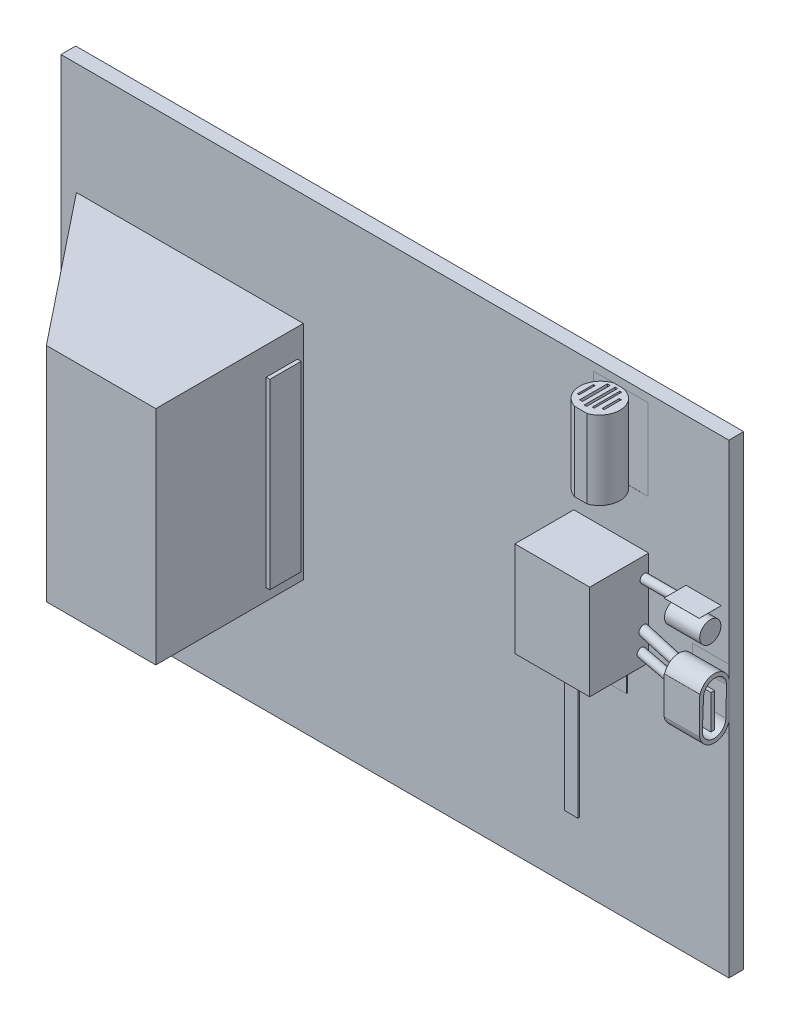
SolidWorks part; units mm, degrees
ref_plane "Front Plane" through (0, 0, 0) normal (0, 0, 1) x (1, 0, 0)
ref_plane "Top Plane" through (0, 0, 0) normal (0, 1, 0) x (1, 0, 0)
ref_plane "Right Plane" through (0, 0, 0) normal (1, 0, 0) x (0, 0, -1)
sketch "Sketch1" plane through (0, 0, 0) normal (0, 0, 1) x (1, 0, 0)
  line L1 (-83.6964, -45.2831) -> (2.5697, -45.2831)
  line L2 (-83.6964, -45.2831) -> (-83.6964, 12.5794)
  line L3 (-83.6964, 12.5794) -> (2.5697, 12.5794)
  line L4 (2.5697, -45.2831) -> (2.5697, 12.5794)
  line L5 (-83.6964, -45.2831) -> (2.5697, 12.5794) construction
  line L6 (-83.6964, 12.5794) -> (2.5697, -45.2831) construction
  point P0 (-40.5634, -16.3519)
extrude "Boss-Extrude1" add sketch "Sketch1" along normal blind 5
sketch "Sketch2" plane through (0, 0, 0) normal (0, 0, -1) x (-1, 0, 0)
  line L1 (50.5486, -38.5474) -> (14.2877, -38.5474)
  line L2 (50.5486, -38.5474) -> (50.5486, 6.6921)
  line L3 (50.5486, 6.6921) -> (14.2877, 6.6921)
  line L4 (14.2877, -38.5474) -> (14.2877, 6.6921)
  line L5 (50.5486, -38.5474) -> (14.2877, 6.6921) construction
  line L6 (50.5486, 6.6921) -> (14.2877, -38.5474) construction
  line L7 (49.8095, -37.7028) -> (15.0267, -37.7028)
  line L8 (49.8095, -37.7028) -> (49.8095, 5.8475)
  line L9 (49.8095, 5.8475) -> (15.0267, 5.8475)
  line L10 (15.0267, -37.7028) -> (15.0267, 5.8475)
  line L11 (49.8095, -37.7028) -> (15.0267, 5.8475) construction
  line L12 (49.8095, 5.8475) -> (15.0267, -37.7028) construction
  point P0 (32.4181, -15.9276)
  point P6 (32.4181, -15.9276)
extrude "Boss-Extrude2" add sketch "Sketch2" along normal blind 1
sketch "Sketch3" plane through (0, 0, 0) normal (0, 0, -1) x (-1, 0, 0)
  circle A0 centre (5.8472, -15.8094) radius 3.5601
extrude "Boss-Extrude3" add sketch "Sketch3" along normal blind 1
sketch "Sketch4" plane through (0, 0, -1) normal (0, 0, -1) x (-1, 0, 0)
  line L0 (7.4982, -13.5037) -> (7.4299, -14.2268)
  line L1 (7.3138, -18.3414) -> (7.3192, -17.6008)
  arc A0 (7.4982, -13.5037) -> (7.3138, -18.3414) centre (5.955, -15.8672) ccw
  arc A1 (7.4299, -14.2268) -> (7.3192, -17.6008) centre (5.955, -15.8672) ccw
extrude "Cut-Extrude2" cut sketch "Sketch4" against normal blind 0.5
sketch "Sketch5" plane through (0, 0, -1) normal (0, 0, -1) x (-1, 0, 0)
  line L0 (8.3401, -15.4929) -> (5.464, -15.4382)
  line L1 (8.3401, -16.1787) -> (5.464, -16.2334)
  arc A0 (8.3401, -16.1787) -> (8.3401, -15.4929) centre (8.3401, -15.8358) ccw
  arc A1 (5.464, -15.4382) -> (5.464, -16.2334) centre (5.464, -15.8358) ccw
extrude "Cut-Extrude3" cut sketch "Sketch5" against normal blind 0.5
sketch "Sketch11" plane through (0, 0, 5) normal (0, 0, 1) x (1, 0, 0)
  line L1 (-85.049, -48.3572) -> (5.5329, -48.3572)
  line L2 (-85.049, -48.3572) -> (-85.049, 14.8126)
  line L3 (-85.049, 14.8126) -> (5.5329, 14.8126)
  line L4 (5.5329, -48.3572) -> (5.5329, 14.8126)
  line L5 (-85.049, -48.3572) -> (5.5329, 14.8126) construction
  line L6 (-85.049, 14.8126) -> (5.5329, -48.3572) construction
  point P0 (-39.7581, -16.7723)
extrude "Boss-Extrude4" add sketch "Sketch11" along normal blind 2
sketch "Sketch12" plane through (2.5697, 0, 0) normal (1, 0, 0) x (0, 0, -1)
  line L0 (-5.0495, 12.5555) -> (1.3768, 8.6378)
  line L1 (1.3768, 8.6378) -> (1.4949, 17.885)
  line L2 (1.4949, 17.885) -> (-5.0495, 12.5555)
extrude "Cut-Extrude11" cut sketch "Sketch12" against normal through all
sketch "Sketch14" plane through (-85.049, 0, 0) normal (-1, 0, 0) x (0, 0, 1)
  line L0 (5, -45.2349) -> (-1.3308, -41.1782)
  line L1 (5, 12.5253) -> (5, -48.3572) construction
  line L2 (-1.3308, -41.1782) -> (-1.6233, -49.506)
  line L3 (-1.6233, -49.506) -> (5, -45.2349)
extrude "Cut-Extrude15" cut sketch "Sketch14" against normal through all
sketch "Sketch15" plane through (0, -48.3572, 0) normal (0, -1, 0) x (-1, 0, 0)
  line L0 (-2.5596, -5) -> (1.7788, 1.2395)
  line L1 (85.049, -5) -> (-5.5329, -5) construction
  line L2 (1.7788, 1.2395) -> (-4.0713, 1.1275)
  line L3 (-4.0713, 1.1275) -> (-2.5596, -5)
extrude "Cut-Extrude18" cut sketch "Sketch15" against normal through all
sketch "Sketch19" plane through (0, -48.3572, 0) normal (0, -1, 0) x (-1, 0, 0)
  line L0 (83.7172, -5) -> (87.2746, 1.6454)
  line L1 (85.049, -5) -> (-5.5329, -5) construction
  line L2 (87.2746, 1.6454) -> (78.5287, 2.7469)
  line L3 (78.5287, 2.7469) -> (83.7172, -5)
extrude "Cut-Extrude21" cut sketch "Sketch19" against normal through all
sketch "Sketch22" plane through (0, 0, 7) normal (0, 0, 1) x (1, 0, 0)
  line L1 (-82.9526, -0.3433) -> (-52.184, -0.3433)
  line L2 (-82.9526, -0.3433) -> (-82.9526, -30.4515)
  line L3 (-82.9526, -30.4515) -> (-52.184, -30.4515)
  line L4 (-52.184, -0.3433) -> (-52.184, -30.4515)
  line L5 (-82.9526, -0.3433) -> (-52.184, -30.4515) construction
  line L6 (-82.9526, -30.4515) -> (-52.184, -0.3433) construction
  point P0 (-67.5683, -15.3974)
extrude "Boss-Extrude9" add sketch "Sketch22" along normal blind 20
sketch "Sketch23" plane through (-55.4815, 0, -37.1587) normal (-0.8309, 0, -0.5565) x (-0.5565, 0, 0.8309)
  line L0 (50.7032, -28.438) -> (50.7032, -4.3391)
  line L1 (50.7032, 12.5064) -> (50.7032, -45.2151) construction
  line L2 (50.7032, -4.3391) -> (35.7393, -4.3391)
  line L3 (35.7393, -4.3391) -> (35.7393, -28.6863)
  line L4 (35.7393, -28.6863) -> (50.7032, -28.438)
extrude "Cut-Extrude25" cut sketch "Sketch23" against normal blind 30
sketch "Sketch24" plane through (0, 0, 0) normal (0, 0, -1) x (-1, 0, 0)
  line L0 (80.3685, -4.3391) -> (64.2248, -4.3391) construction
  line L1 (53.8212, -28.6863) -> (64.2248, -28.6863)
  line L2 (53.8212, -28.6863) -> (53.8212, -4.3391)
  line L3 (53.8212, -4.3391) -> (64.2248, -4.3391)
  line L4 (64.2248, -28.6863) -> (64.2248, -4.3391)
  line L5 (53.8212, -28.6863) -> (64.2248, -4.3391) construction
  line L6 (53.8212, -4.3391) -> (64.2248, -28.6863) construction
  line L7 (64.2248, -4.3391) -> (64.2248, -28.6863) construction
  point P0 (59.023, -16.5127)
extrude "Cut-Extrude27" cut sketch "Sketch24" against normal blind 7
sketch "Sketch25" plane through (0, -30.4515, 0) normal (0, -1, 0) x (-1, 0, 0)
  line L0 (67.027, -27) -> (82.9526, -7)
  line L1 (82.9526, -27) -> (52.184, -27) construction
  line L2 (82.9526, -7) -> (82.9526, -27)
  line L3 (82.9526, -27) -> (82.9526, -7) construction
  line L4 (82.9526, -27) -> (67.027, -27)
extrude "Cut-Extrude29" cut sketch "Sketch25" against normal through all
sketch "Sketch26" plane through (-28.2149, 0, 42.1276) normal (0.5565, 0, -0.8309) x (-0.8309, 0, -0.5565)
  line L0 (54.7061, -26.9497) -> (51.42, -27.0426)
  line L1 (51.42, -27.0426) -> (49.1981, -24.943)
  line L2 (49.1981, -24.943) -> (49.1134, -21.9477)
  line L3 (49.1134, -21.9477) -> (51.379, -19.9792)
  line L4 (51.379, -19.9792) -> (54.3761, -19.7757)
  line L5 (54.3761, -19.7757) -> (56.7869, -21.3756)
  line L6 (56.7869, -21.3756) -> (56.7869, -24.7523)
  line L7 (56.7869, -24.7523) -> (54.7061, -26.9497)
  line L8 (54.7061, -26.4154) -> (51.5118, -26.5172)
  line L9 (51.5118, -26.5172) -> (49.6724, -24.7913)
  line L10 (49.6724, -24.7913) -> (49.5843, -22.0272)
  line L11 (49.5843, -22.0272) -> (51.5118, -20.3421)
  line L13 (54.292, -20.113) -> (56.4421, -21.5046)
  line L14 (56.4421, -21.5046) -> (56.4421, -24.6328)
  line L15 (56.4421, -24.6328) -> (54.7061, -26.4154)
  line L16 (54.292, -20.113) -> (51.4865, -20.3421)
extrude "Boss-Extrude12" add sketch "Sketch26" along normal blind 0.5 contours L7 L6 L5 L4 L3 L2 L1 L0 region at (-72.2604, -23.4058, 12.6282)
sketch "Sketch27" plane through (-27.9367, 0, 41.7122) normal (0.5565, 0, -0.8309) x (-0.8309, 0, -0.5565)
  line L0 (54.4646, -26.3342) -> (51.6468, -26.4613)
  line L1 (51.6468, -26.4613) -> (49.7838, -24.7591)
  line L2 (49.7838, -24.7591) -> (49.7838, -22.033)
  line L3 (49.7838, -22.033) -> (51.4884, -20.6267)
  line L4 (51.4884, -20.6267) -> (54.0987, -20.567)
  line L5 (54.0987, -20.567) -> (56.1639, -21.7042)
  line L6 (56.1639, -21.7042) -> (56.2319, -24.6811)
  line L7 (56.2319, -24.6811) -> (54.4646, -26.3342)
  line L8 (54.3202, -25.7184) -> (51.7276, -25.7776)
  line L9 (51.7276, -25.7776) -> (50.5704, -24.5406)
  line L10 (50.5704, -24.5406) -> (50.4628, -22.1543)
  line L11 (50.4628, -22.1543) -> (51.4425, -21.2379)
  line L12 (51.4425, -21.2379) -> (54.0133, -21.2379)
  line L13 (54.0133, -21.2379) -> (55.475, -22.0626)
  line L14 (55.475, -22.0626) -> (55.475, -24.5406)
  line L15 (55.475, -24.5406) -> (54.3202, -25.7184)
extrude "Cut-Extrude30" cut sketch "Sketch27" against normal blind 0.5
sketch "Sketch28" plane through (-52.184, 0, 0) normal (1, 0, 0) x (0, 0, -1)
  line L1 (-7.7943, -4.1368) -> (-12.0375, -4.1368)
  line L2 (-7.7943, -4.1368) -> (-7.7943, -28.8565)
  line L3 (-7.7943, -28.8565) -> (-12.0375, -28.8565)
  line L4 (-12.0375, -4.1368) -> (-12.0375, -28.8565)
  line L5 (-7.7943, -4.1368) -> (-12.0375, -28.8565) construction
  line L6 (-7.7943, -28.8565) -> (-12.0375, -4.1368) construction
  point P0 (-9.9159, -16.4967)
extrude "Boss-Extrude13" add sketch "Sketch28" along normal blind 0.5
sketch "Sketch30" plane through (-28.2149, 0, 42.1276) normal (0.5565, 0, -0.8309) x (-0.8309, 0, -0.5565)
  line L0 (39.741, -18.4923) -> (39.4768, -15.4766)
  line L1 (39.4768, -15.4766) -> (41.6727, -13.4395)
  line L2 (41.6727, -13.4395) -> (44.994, -13.0953)
  line L3 (44.994, -13.0953) -> (47.5825, -14.9189)
  line L4 (47.5825, -14.9189) -> (47.5825, -17.5566)
  line L5 (47.5825, -17.5566) -> (45.5971, -19.8398)
  line L6 (45.5971, -19.8398) -> (42.2786, -20.1305)
  line L7 (42.2786, -20.1305) -> (39.741, -18.4923)
  line L8 (42.7534, -19.5576) -> (40.2187, -17.9152)
  line L9 (40.2187, -17.9152) -> (40.0475, -15.6187)
  line L10 (40.0475, -15.6187) -> (41.8581, -13.9959)
  line L11 (41.8581, -13.9959) -> (44.6411, -13.7001)
  line L12 (44.6411, -13.7001) -> (47.0086, -15.2342)
  line L13 (47.0086, -15.2342) -> (47.0876, -17.3469)
  line L14 (47.0876, -17.3469) -> (45.2147, -19.3741)
  line L15 (45.2147, -19.3741) -> (42.7534, -19.5576)
extrude "Boss-Extrude14" add sketch "Sketch30" along normal blind 0.5
sketch "Sketch31" plane through (-28.2149, 0, 42.1276) normal (0.5565, 0, -0.8309) x (-0.8309, 0, -0.5565)
  line L0 (42.8579, -19.0017) -> (40.9087, -17.7098)
  line L1 (40.9087, -17.7098) -> (40.7983, -15.9356)
  line L2 (40.7983, -15.9356) -> (42.2062, -14.4864)
  line L3 (42.2062, -14.4864) -> (44.0287, -14.2678)
  line L4 (44.0287, -14.2678) -> (46.1553, -15.6773)
  line L5 (46.1553, -15.6773) -> (46.2514, -17.2226)
  line L6 (46.2514, -17.2226) -> (44.5885, -18.9343)
  line L7 (44.5885, -18.9343) -> (42.8579, -19.0017)
extrude "Boss-Extrude15" add sketch "Sketch31" along normal blind 0.5
sketch "Sketch33" plane through (-28.2149, 0, 42.1276) normal (0.5565, 0, -0.8309) x (-0.8309, 0, -0.5565)
  line L0 (53.5036, -12.1793) -> (50.3513, -12.1793)
  line L1 (53.5036, -5.7866) -> (50.2502, -5.7866)
  line L2 (53.5036, -12.1793) -> (55.5149, -10.4174)
  line L3 (55.5149, -10.4174) -> (55.5149, -7.3707)
  line L4 (55.5149, -7.3707) -> (53.5036, -5.7866)
  line L5 (50.3513, -12.1793) -> (48.1508, -10.2126)
  line L6 (48.1508, -10.2126) -> (48.1508, -7.1561)
  line L7 (48.1508, -7.1561) -> (50.2502, -5.7866)
  line L8 (53.5036, -11.5928) -> (50.5381, -11.5928)
  line L9 (50.5381, -11.5928) -> (48.7427, -9.9711)
  line L10 (48.7427, -9.9711) -> (48.6105, -7.3707)
  line L11 (48.6105, -7.3707) -> (50.2502, -6.3087)
  line L12 (50.2502, -6.3087) -> (53.3239, -6.3087)
  line L13 (53.3239, -6.3087) -> (54.9664, -7.5403)
  line L14 (54.9664, -7.5403) -> (54.9664, -10.4174)
  line L15 (54.9664, -10.4174) -> (53.5036, -11.5928)
extrude "Boss-Extrude16" add sketch "Sketch33" along normal blind 0.5
sketch "Sketch34" plane through (-28.2149, 0, 42.1276) normal (0.5565, 0, -0.8309) x (-0.8309, 0, -0.5565)
  line L0 (53.1065, -10.9168) -> (50.7972, -10.9168)
  line L1 (50.7972, -10.9168) -> (49.2381, -9.7583)
  line L2 (49.2381, -9.7583) -> (49.2381, -7.7183)
  line L3 (49.2381, -7.7183) -> (50.3642, -6.7724)
  line L4 (50.3642, -6.7724) -> (52.9303, -6.7724)
  line L5 (52.9303, -6.7724) -> (54.1875, -7.7448)
  line L6 (54.1875, -7.7448) -> (54.1875, -9.9905)
  line L7 (54.1875, -9.9905) -> (53.1065, -10.9168)
extrude "Boss-Extrude17" add sketch "Sketch34" along normal blind 0.5
sketch "Sketch35" plane through (-28.2149, 0, 42.1276) normal (0.5565, 0, -0.8309) x (-0.8309, 0, -0.5565)
  line L0 (64.7134, -17.1204) -> (64.7134, -13.8698)
  line L1 (64.7134, -13.8698) -> (62.5655, -12.2617)
  line L2 (62.5655, -12.2617) -> (58.9579, -12.2617)
  line L3 (64.7134, -17.1204) -> (62.5229, -19.1048)
  line L4 (62.5229, -19.1048) -> (59.3824, -19.1048)
  line L5 (59.3824, -19.1048) -> (56.8589, -17.1993)
  line L6 (56.8589, -17.1993) -> (56.8589, -14.2019)
  line L7 (56.8589, -14.2019) -> (58.9579, -12.2617)
  line L8 (62.3869, -18.4035) -> (59.3824, -18.4035)
  line L9 (59.3824, -18.4035) -> (57.5666, -17.0465)
  line L10 (57.5666, -17.0465) -> (57.5666, -14.5319)
  line L11 (57.5666, -14.5319) -> (59.0471, -12.8652)
  line L12 (59.0471, -12.8652) -> (62.5655, -12.8652)
  line L13 (62.5655, -12.8652) -> (63.9381, -13.891)
  line L14 (63.9381, -13.891) -> (63.9381, -16.9379)
  line L15 (63.9381, -16.9379) -> (62.3869, -18.4035)
extrude "Boss-Extrude18" add sketch "Sketch35" along normal blind 0.5
sketch "Sketch36" plane through (-28.2149, 0, 42.1276) normal (0.5565, 0, -0.8309) x (-0.8309, 0, -0.5565)
  line L0 (61.8697, -17.4964) -> (59.9308, -17.4964)
  line L1 (59.9308, -17.4964) -> (58.7161, -16.6958)
  line L2 (58.7161, -16.6958) -> (58.52, -14.7296)
  line L3 (58.52, -14.7296) -> (59.3629, -13.4509)
  line L4 (59.3629, -13.4509) -> (61.6665, -13.4509)
  line L5 (61.6665, -13.4509) -> (62.906, -14.2679)
  line L6 (62.906, -14.2679) -> (62.906, -16.3755)
  line L7 (62.906, -16.3755) -> (61.8697, -17.4964)
extrude "Boss-Extrude19" add sketch "Sketch36" along normal blind 0.5
sketch "Sketch37" plane through (0, 0, 7) normal (0, 0, 1) x (1, 0, 0)
  line L1 (5.5683, -11.5042) -> (0.7589, -11.5042)
  line L2 (5.5683, -11.5042) -> (5.5683, -19.728)
  line L3 (5.5683, -19.728) -> (0.7589, -19.728)
  line L4 (0.7589, -11.5042) -> (0.7589, -19.728)
  line L5 (5.5683, -11.5042) -> (0.7589, -19.728) construction
  line L6 (5.5683, -19.728) -> (0.7589, -11.5042) construction
  point P0 (3.1636, -15.6161)
extrude "Boss-Extrude20" add sketch "Sketch37" along normal blind 4
sketch "Sketch38" plane through (5.5683, 0, 0) normal (1, 0, 0) x (0, 0, -1)
  line L2 (-11, -19.728) -> (-11, -11.5042) construction
  line L3 (-6.9987, -13.4166) -> (-7, -11.5042)
  line L4 (-11, -11.5042) -> (-7, -11.5042) construction
  line L5 (-7, -19.728) -> (-7, -11.5042) construction
  line L6 (-7, -11.5042) -> (-11, -11.5042)
  line L7 (-11, -11.5042) -> (-10.999, -13.2842)
  line L8 (-11, -18.0496) -> (-11, -19.728)
  line L9 (-11, -19.728) -> (-7, -19.728)
  line L10 (-11, -19.728) -> (-7, -19.728) construction
  line L11 (-7, -19.728) -> (-6.9992, -18.0723)
  arc A1 (-11, -18.0496) -> (-6.9992, -18.0723) centre (-8.9975, -17.692) ccw
  arc A2 (-6.9987, -13.4166) -> (-10.999, -13.2842) centre (-9.0073, -13.6054) ccw
extrude "Cut-Extrude31" cut sketch "Sketch38" against normal blind 5
sketch "Sketch39" plane through (0.7589, 0, 0) normal (-1, 0, 0) x (0, 0, 1)
  line L0 (10.9368, -12.8917) -> (11.5567, -14.0619)
  line L1 (11.5567, -14.0619) -> (12.3287, -11.916)
  line L2 (12.3287, -11.916) -> (10.8911, -11.0395)
  line L3 (10.8911, -11.0395) -> (10.9368, -12.8917)
extrude "Cut-Extrude32" cut sketch "Sketch39" against normal blind 5
sketch "Sketch40" plane through (5.5683, 0, 0) normal (1, 0, 0) x (0, 0, -1)
  line L0 (-7.3531, -13.699) -> (-7.449, -17.5958)
  line L1 (-10.478, -13.699) -> (-10.6316, -17.5208)
  arc A0 (-7.355, -13.7759) -> (-10.478, -13.699) centre (-8.9156, -13.699) ccw
  arc A1 (-10.6316, -17.5208) -> (-7.449, -17.5958) centre (-9.0412, -17.5958) ccw
extrude "Cut-Extrude33" cut sketch "Sketch40" against normal blind 4 contours L1 A1 L0 A0 region at (5.5683, -15.6728, 8.9791)
sketch "Sketch41" plane through (1.5683, 0, 0) normal (1, 0, 0) x (0, 0, -1)
  line L0 (-8.9553, -13.6084) -> (-8.9553, -18.2137)
  line L1 (-8.9553, -18.2137) -> (-9.4722, -18.2137)
  line L2 (-9.4722, -18.2137) -> (-9.4722, -13.5662)
  line L3 (-9.4722, -13.5662) -> (-8.9553, -13.6084)
extrude "Boss-Extrude21" add sketch "Sketch41" along normal blind 4
sketch "Sketch45" plane through (0, 0, 7) normal (0, 0, 1) x (1, 0, 0)
  line L1 (-5.4203, 3.106) -> (-12.8133, 3.106)
  line L2 (-5.4203, 3.106) -> (-5.4203, 13.7297)
  line L3 (-5.4203, 13.7297) -> (-12.8133, 13.7297)
  line L4 (-12.8133, 3.106) -> (-12.8133, 13.7297)
  line L5 (-5.4203, 3.106) -> (-12.8133, 13.7297) construction
  line L6 (-5.4203, 13.7297) -> (-12.8133, 3.106) construction
  point P0 (-9.1168, 8.4178)
extrude "Boss-Extrude24" add sketch "Sketch45" along normal blind 5.4
sketch "Sketch49" plane through (0, 13.7297, 0) normal (0, 1, 0) x (1, 0, 0)
  line L4 (-9.9701, -6.9787) -> (-12.8133, -7)
  line L5 (-12.8133, -12.4) -> (-12.8133, -7) construction
  line L6 (-12.8133, -7) -> (-12.8133, -12.4)
  line L7 (-5.4203, -12.4) -> (-12.8133, -12.4) construction
  line L8 (-12.8133, -12.4) -> (-9.9877, -12.4)
  arc A0 (-9.9701, -6.9787) -> (-9.9877, -12.4) centre (-9.1757, -9.692) ccw
extrude "Cut-Extrude47" cut sketch "Sketch49" against normal blind 11
sketch "Sketch54" plane through (0, 13.7297, 0) normal (0, 1, 0) x (1, 0, 0)
  line L0 (-9.2372, -6.985) -> (-5.4203, -7)
  line L1 (-5.4203, -7) -> (-5.4203, -12.4)
  line L2 (-5.4203, -12.4) -> (-8.2825, -12.4022)
  arc A0 (-8.2825, -12.4022) -> (-9.2372, -6.985) centre (-9.2482, -9.7797) ccw
extrude "Cut-Extrude48" cut sketch "Sketch54" against normal blind 11
sketch "Sketch55" plane through (0, 13.7297, 0) normal (0, 1, 0) x (1, 0, 0)
  line L1 (-9.4942, -7.3991) -> (-9.1555, -7.3991)
  line L2 (-9.4942, -7.3991) -> (-9.4942, -11.5965)
  line L3 (-9.4942, -11.5965) -> (-9.1555, -11.5965)
  line L4 (-9.1555, -7.3991) -> (-9.1555, -11.5965)
  line L5 (-9.4942, -7.3991) -> (-9.1555, -11.5965) construction
  line L6 (-9.4942, -11.5965) -> (-9.1555, -7.3991) construction
  line L7 (-10.4091, -7.5449) -> (-10.0225, -7.5449)
  line L8 (-10.4091, -7.5449) -> (-10.4091, -11.2966)
  line L9 (-10.4091, -11.2966) -> (-10.0225, -11.2966)
  line L10 (-10.0225, -7.5449) -> (-10.0225, -11.2966)
  line L11 (-10.4091, -7.5449) -> (-10.0225, -11.2966) construction
  line L12 (-10.4091, -11.2966) -> (-10.0225, -7.5449) construction
  line L13 (-11.2656, -8.5761) -> (-11.0296, -8.5761)
  line L14 (-11.2656, -8.5761) -> (-11.2656, -10.7521)
  line L15 (-11.2656, -10.7521) -> (-11.0296, -10.7521)
  line L16 (-11.0296, -8.5761) -> (-11.0296, -10.7521)
  line L17 (-11.2656, -8.5761) -> (-11.0296, -10.7521) construction
  line L18 (-11.2656, -10.7521) -> (-11.0296, -8.5761) construction
  line L19 (-8.6997, -7.5449) -> (-8.4451, -7.5449)
  line L20 (-8.6997, -7.5449) -> (-8.6997, -11.2966)
  line L21 (-8.6997, -11.2966) -> (-8.4451, -11.2966)
  line L22 (-8.4451, -7.5449) -> (-8.4451, -11.2966)
  line L23 (-8.6997, -7.5449) -> (-8.4451, -11.2966) construction
  line L24 (-8.6997, -11.2966) -> (-8.4451, -7.5449) construction
  line L25 (-7.8715, -8.4633) -> (-7.5893, -8.4633)
  line L26 (-7.8715, -8.4633) -> (-7.8715, -10.7921)
  line L27 (-7.8715, -10.7921) -> (-7.5893, -10.7921)
  line L28 (-7.5893, -8.4633) -> (-7.5893, -10.7921)
  line L29 (-7.8715, -8.4633) -> (-7.5893, -10.7921) construction
  line L30 (-7.8715, -10.7921) -> (-7.5893, -8.4633) construction
  point P0 (-9.3248, -9.4978)
  point P5 (-10.2158, -9.4207)
  point P10 (-11.1476, -9.6641)
  point P15 (-8.5724, -9.4207)
  point P20 (-7.7304, -9.6277)
extrude "Cut-Extrude49" cut sketch "Sketch55" against normal blind 2
sketch "Sketch57" plane through (0, 0, 7) normal (0, 0, 1) x (1, 0, 0)
  line L1 (4.5041, -9.5545) -> (-0.2735, -9.5545)
  line L2 (4.5041, -9.5545) -> (4.5041, -5.1345)
  line L3 (4.5041, -5.1345) -> (-0.2735, -5.1345)
  line L4 (-0.2735, -9.5545) -> (-0.2735, -5.1345)
  line L5 (4.5041, -9.5545) -> (-0.2735, -5.1345) construction
  line L6 (4.5041, -5.1345) -> (-0.2735, -9.5545) construction
  point P0 (2.1153, -7.3445)
extrude "Boss-Extrude25" add sketch "Sketch57" along normal blind 3
sketch "Sketch58" plane through (0, 0, 7) normal (0, 0, 1) x (1, 0, 0)
  line L1 (-5.3426, -16.7692) -> (-15.4966, -16.7692)
  line L2 (-5.3426, -16.7692) -> (-5.3426, -3.8844)
  line L3 (-5.3426, -3.8844) -> (-15.4966, -3.8844)
  line L4 (-15.4966, -16.7692) -> (-15.4966, -3.8844)
  line L5 (-5.3426, -16.7692) -> (-15.4966, -3.8844) construction
  line L6 (-5.3426, -3.8844) -> (-15.4966, -16.7692) construction
  point P0 (-10.4196, -10.3268)
extrude "Boss-Extrude26" add sketch "Sketch58" along normal blind 8
sketch "Sketch60" plane through (4.5041, 0, 0) normal (1, 0, 0) x (0, 0, -1)
  line L0 (-7, -9.5545) -> (-10, -9.5545)
  line L1 (-10, -9.5545) -> (-7, -9.5545) construction
  line L2 (-10, -9.5545) -> (-10, -5.1345) construction
  line L3 (-10, -9.5545) -> (-10, -5.1388)
  line L4 (-10, -5.1388) -> (-7, -5.1345)
  line L5 (-10, -5.1345) -> (-7, -5.1345) construction
  line L6 (-7, -5.1345) -> (-7, -9.5545)
  circle A0 centre (-8.4911, -7.4729) radius 1.4368
extrude "Cut-Extrude50" cut sketch "Sketch60" against normal blind 5
sketch "Sketch64" plane through (0.7589, 0, 0) normal (-1, 0, 0) x (0, 0, 1)
  circle A0 centre (7.6879, -14.3695) radius 0.6521
sketch "Sketch65" plane through (0.7589, 0, 0) normal (-1, 0, 0) x (0, 0, 1)
  circle A0 centre (7.6749, -16.8671) radius 0.5799
sketch3d "3DSketch4"
  line L0 (0.7589, -16.8671, 7.6749) -> (-5.385, -15.0352, 7.9885)
sweep "Sweep4" add profiles "Sketch65" path "3DSketch4"
sketch3d "3DSketch5"
  line L0 (0.7589, -14.3695, 7.6879) -> (-5.5706, -12.5373, 7.6785)
sweep "Sweep5" add profiles "Sketch64" path "3DSketch5"
sketch "Sketch66" plane through (0, -16.7692, 0) normal (0, -1, 0) x (-1, 0, 0)
  line L2 (9.8594, -12.081) -> (9.8594, -11.8879)
  line L3 (9.8594, -11.8879) -> (11.7228, -11.8879)
  line L5 (11.7228, -11.8879) -> (11.7228, -12.0392)
  line L6 (11.7228, -12.0392) -> (9.8594, -12.081)
extrude "Boss-Extrude27" add sketch "Sketch66" along normal blind 18
sketch "Sketch67" plane through (0, -16.7692, 0) normal (0, -1, 0) x (-1, 0, 0)
  line L0 (10.6998, -7) -> (10.6998, -7.1445)
  line L1 (15.4966, -7) -> (5.3426, -7) construction
  line L2 (10.6998, -7.1445) -> (8.2189, -7.1445)
  line L3 (8.2189, -7.1445) -> (8.2189, -7)
  line L4 (8.2189, -7) -> (10.6998, -7)
extrude "Boss-Extrude28" add sketch "Sketch67" along normal blind 5
sketch "Sketch68" plane through (-5.3426, 0, 0) normal (1, 0, 0) x (0, 0, -1)
  circle A0 centre (-7.5932, -6.5649) radius 0.579
sketch3d "3DSketch7"
  line L0 (-5.3426, -6.5649, 7.5932) -> (0.9546, -6.5649, 7.5932)
sweep "Sweep8" add profiles "Sketch68" path "3DSketch7"
